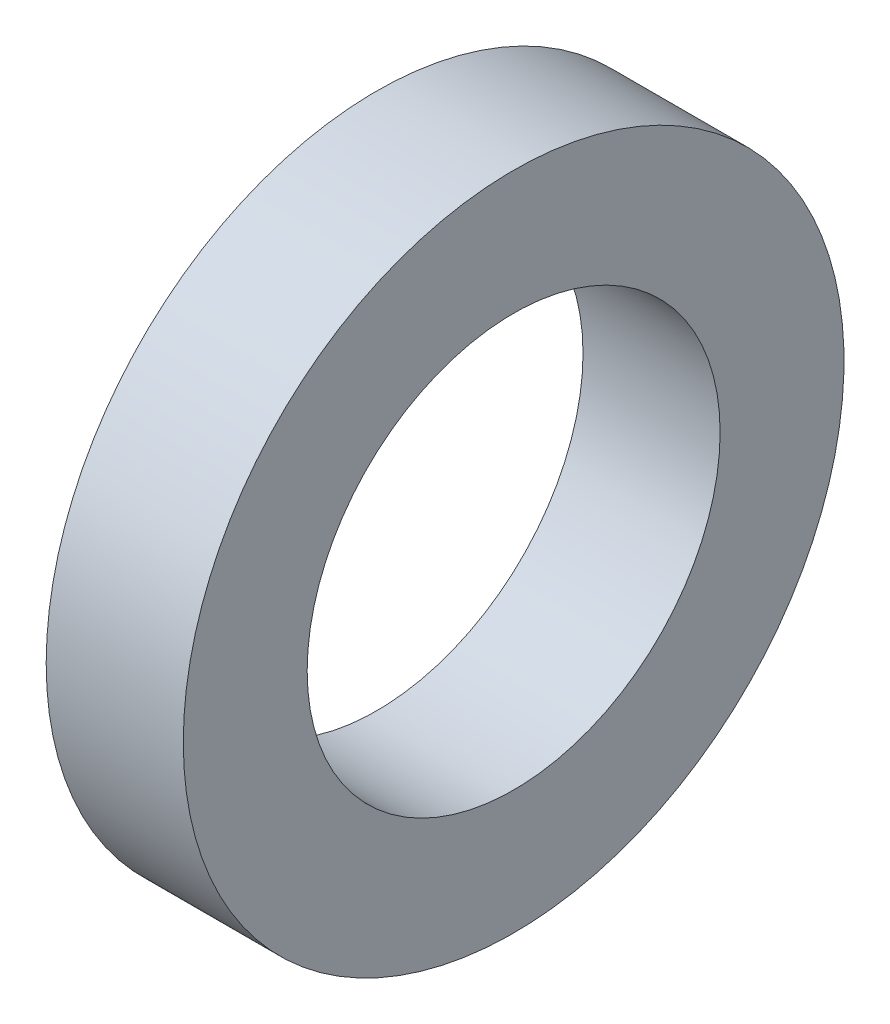
SolidWorks part; units mm, degrees
ref_plane "Front Plane" through (0, 0, 0) normal (0, 0, 1) x (1, 0, 0)
ref_plane "Top Plane" through (0, 0, 0) normal (0, 1, 0) x (1, 0, 0)
ref_plane "Right Plane" through (0, 0, 0) normal (1, 0, 0) x (0, 0, -1)
sketch "Sketch2" plane through (0, 0, 0) normal (0, 0, 1) x (1, 0, 0)
  line L0 (0, 0) -> (58.591, 0) construction
  line L2 (0, 0) -> (18.4, 0)
  line L3 (0, 0) -> (0, 2.5)
  line L4 (0, 2.5) -> (18.4, 2.5)
  line L5 (18.4, 0) -> (18.4, 2.5)
  line L6 (6, 2.5) -> (6, 6)
  line L11 (6, 6) -> (9.97, 6)
  line L16 (12.97, 6) -> (12.97, 3)
  line L17 (12.97, 3) -> (13.6304, 3)
  line L18 (13.6304, 3) -> (13.6304, 2.5)
  line L19 (13.6304, 2.5) -> (6, 2.5)
  line L22 (13.6304, 2.5) -> (16.1104, 2.5)
  line L23 (13.6304, 2.5) -> (13.6304, 4)
  line L24 (13.6304, 4) -> (16.1104, 4)
  line L25 (16.1104, 2.5) -> (16.1104, 4)
  line L27 (6, 6) -> (9.97, 6)
  line L28 (6, 6) -> (6, 9)
  line L29 (6, 9) -> (9.97, 9)
  line L30 (9.97, 6) -> (9.97, 9)
  line L31 (6, 9) -> (6, 8.25)
  line L32 (6, 8.25) -> (5, 8.25)
  line L33 (8.58, 22.001) -> (8.58, 12.476) construction
  line L34 (5, 12.476) -> (12.16, 12.476)
  line L35 (9.97, 9) -> (12.16, 9)
  line L36 (5, 7.5) -> (3, 7.5)
  line L37 (5, 8.25) -> (5, 12.476)
  line L38 (5, 7.5) -> (5, 14)
  line L39 (5, 14) -> (3, 14)
  line L40 (3, 7.5) -> (3, 14)
  line L41 (5, 22.001) -> (12.16, 22.001)
  line L42 (5, 22.001) -> (5, 30.1625)
  line L43 (5, 30.1625) -> (12.16, 30.1625)
  line L44 (12.16, 22.001) -> (12.16, 30.1625)
  line L49 (16.6304, 22.001) -> (16.6304, 7.5)
  line L51 (23.0104, 7.5) -> (23.0104, 6.5)
  line L54 (16.1104, 4) -> (13.6304, 4)
  line L56 (18.0304, 7.5) -> (23.0104, 7.5)
  line L57 (13.16, 22.001) -> (16.6304, 22.001)
  line L58 (16.1104, 3.5) -> (20.0104, 3.5)
  line L59 (29.9004, 14) -> (26.9004, 11)
  line L60 (4, 31.75) -> (18.0304, 31.75)
  line L61 (18.0304, 7.5) -> (23.0104, 7.5)
  line L62 (18.0304, 7.5) -> (18.0304, 12)
  line L63 (18.0304, 12) -> (23.0104, 12)
  line L64 (23.0104, 7.5) -> (23.0104, 12)
  line L65 (18.0304, 31.75) -> (18.0304, 12)
  line L66 (23.0104, 11) -> (26.9004, 11)
  line L67 (34.8004, 23) -> (31.3004, 19.5)
  line L68 (35.8004, 31) -> (38.7904, 33.99)
  line L69 (29.9004, 14) -> (29.9004, 15)
  line L70 (29.9004, 15) -> (22.9304, 15)
  line L71 (22.9304, 15) -> (21.0304, 15)
  line L72 (18.0304, 7.5) -> (16.6304, 7.5)
  line L73 (21.0304, 15) -> (21.0304, 43)
  line L74 (20.0304, 40) -> (10.0704, 40)
  line L75 (10.0704, 40) -> (4, 40)
  line L76 (21.0304, 43) -> (20.0304, 43)
  line L77 (22.9304, 15) -> (29.9004, 15)
  line L78 (22.9304, 15) -> (22.9304, 21)
  line L79 (22.9304, 21) -> (29.9004, 21)
  line L80 (29.9004, 15) -> (29.9004, 21)
  line L81 (10.0704, 40) -> (20.0304, 40)
  line L82 (10.0704, 40) -> (10.0704, 50)
  line L83 (10.0704, 50) -> (20.0304, 50)
  line L84 (20.0304, 40) -> (20.0304, 50)
  line L85 (4, 40) -> (4, 31.75)
  line L86 (12.97, 3) -> (12.97, 2.5)
  line L87 (31.3004, 19.5) -> (29.9004, 19.5)
  line L88 (21.51, 63.5) -> (21.51, 44)
  line L89 (21.51, 63.5) -> (25.9304, 63.5)
  line L90 (25.9304, 63.5) -> (25.9304, 25)
  line L91 (27.8304, 25) -> (25.9304, 25)
  line L92 (10.0704, 48) -> (9, 48)
  line L93 (9, 48) -> (9, 53.476)
  line L94 (9, 53.476) -> (20.0304, 53.476)
  line L95 (20.0304, 53.476) -> (20.0304, 50)
  line L96 (14.5152, 63.001) -> (14.5152, 53.476) construction
  line L97 (9, 63.001) -> (20.0304, 63.001)
  line L98 (9, 63.001) -> (9, 68.2625)
  line L99 (9, 68.2625) -> (20.0304, 68.2625)
  line L100 (20.0304, 63.001) -> (20.0304, 68.2625)
  line L101 (12.97, 6) -> (11.97, 6)
  line L102 (9, 42.5) -> (5, 42.5)
  line L103 (9, 42.5) -> (9, 55)
  line L104 (9, 55) -> (5, 55)
  line L105 (5, 42.5) -> (5, 55)
  line L106 (9.97, 6) -> (10.87, 6)
  line L107 (27.8304, 25) -> (34.8004, 25)
  line L108 (34.8004, 25) -> (34.8004, 23)
  line L109 (0, 0) -> (-2, 0)
  line L110 (0, 0) -> (0, 11)
  line L111 (27.8304, 25) -> (34.8004, 25)
  line L112 (27.8304, 25) -> (27.8304, 32.5)
  line L113 (27.8304, 32.5) -> (34.8004, 32.5)
  line L114 (34.8004, 25) -> (34.8004, 32.5)
  line L115 (35.8004, 31) -> (34.8004, 31)
  line L116 (27.8304, 32.5) -> (27.8304, 64.5)
  line L117 (21.1827, 74.025) -> (6.8477, 74.025)
  line L118 (6.8477, 74.025) -> (6.8477, 76.2)
  line L119 (38.7904, 47.29) -> (30.8304, 55.25)
  line L120 (0, 11) -> (-2, 11)
  line L121 (38.7904, 43.815) -> (30.8529, 43.815)
  line L123 (-4.8, 69.85) -> (1.55, 76.2)
  line L124 (38.7904, 47.29) -> (38.7904, 33.99)
  line L125 (-2, 0) -> (-2, 11)
  line L126 (38.7904, 37.465) -> (30.8529, 37.465)
  line L127 (30.8529, 43.815) -> (30.8529, 37.465)
  line L128 (6, 2.5) -> (6, 0)
  line L129 (0, 63.5) -> (0, 30)
  line L132 (5, 63.5) -> (0, 63.5)
  line L136 (-1.8, 30) -> (-11.76, 30)
  line L138 (-13.76, 25.4) -> (-2, 25.4)
  line L139 (-2, 25.4) -> (-2, 11.5)
  line L140 (27.8304, 64.5) -> (21.1827, 64.5)
  line L141 (-1.8, 30) -> (-11.76, 30)
  line L142 (-1.8, 30) -> (-1.8, 39)
  line L143 (-1.8, 39) -> (-11.76, 39)
  line L144 (-11.76, 30) -> (-11.76, 39)
  line L145 (21.1827, 64.5) -> (21.1827, 74.025)
  line L146 (-12.76, 37) -> (-12.76, 47.29)
  line L147 (-12.76, 37) -> (-11.76, 37)
  line L148 (30.8304, 55.25) -> (30.8304, 76.2)
  line L149 (11.97, 6) -> (11.97, 5.45)
  line L154 (-2, 11.5) -> (1, 11.5)
  line L155 (5, 60.6197) -> (24.05, 60.6197)
  line L160 (5, 60.6197) -> (5, 55.8572)
  line L161 (5, 55.8572) -> (24.05, 55.8572)
  line L166 (24.05, 60.6197) -> (24.05, 55.8572)
  line L167 (5, 60.6197) -> (24.05, 55.8572) construction
  line L172 (5, 55.8572) -> (24.05, 60.6197) construction
  line L173 (24.05, 62.2072) -> (25.9304, 62.2072)
  line L174 (11.97, 5.45) -> (10.87, 5.45)
  line L175 (10.87, 6) -> (10.87, 5.45)
  line L176 (24.05, 62.2072) -> (24.05, 54.2697)
  line L177 (24.05, 54.2697) -> (25.9304, 54.2697)
  line L178 (25.9304, 62.2072) -> (25.9304, 54.2697)
  line L179 (24.05, 62.2072) -> (25.9304, 54.2697) construction
  line L180 (24.05, 54.2697) -> (25.9304, 62.2072) construction
  line L181 (3, 19.6197) -> (15.7, 19.6197)
  line L182 (3, 19.6197) -> (3, 14.8572)
  line L183 (3, 14.8572) -> (15.7, 14.8572)
  line L184 (15.7, 19.6197) -> (15.7, 14.8572)
  line L185 (3, 19.6197) -> (15.7, 14.8572) construction
  line L186 (3, 14.8572) -> (15.7, 19.6197) construction
  line L187 (15.7, 21.2072) -> (16.6304, 21.2072)
  line L188 (15.7, 21.2072) -> (15.7, 13.2697)
  line L189 (15.7, 13.2697) -> (16.6304, 13.2697)
  line L190 (16.6304, 21.2072) -> (16.6304, 13.2697)
  line L191 (15.7, 21.2072) -> (16.6304, 13.2697) construction
  line L192 (15.7, 13.2697) -> (16.6304, 21.2072) construction
  line L193 (1, 11.5) -> (1, 6.5)
  line L194 (1, 6.5) -> (3, 6.5)
  line L195 (23.0104, 6.5) -> (20.0104, 3.5)
  line L196 (5, 63.5) -> (5, 42.5)
  line L197 (5, 42.5) -> (3, 42.5)
  line L198 (3, 42.5) -> (3, 6.5)
  line L199 (6, 0) -> (12.97, 0)
  line L200 (12.97, 0) -> (12.97, 2.5)
  line L201 (18.0304, 31.75) -> (18.0304, 35.875)
  line L202 (18.0304, 35.875) -> (21.0304, 35.875)
  line L203 (30.8304, 76.2) -> (6.8477, 76.2)
  line L204 (3.4027, 69.85) -> (7.8477, 69.85) construction
  line L205 (7.8477, 67.4687) -> (26.8977, 67.4688)
  line L206 (7.8477, 74.025) -> (7.8477, 64.5)
  line L207 (7.8477, 64.5) -> (-1.8, 64.5)
  line L208 (-1.8, 64.5) -> (-1.8, 39)
  line L209 (-12.76, 47.29) -> (-4.8, 55.25)
  line L210 (-4.8, 55.25) -> (-4.8, 69.85)
  line L211 (7.8477, 67.4687) -> (7.8477, 72.2313)
  line L212 (7.8477, 72.2313) -> (26.8977, 72.2313)
  line L213 (26.8977, 67.4688) -> (26.8977, 72.2313)
  line L214 (26.8977, 73.8187) -> (30.8304, 73.8187)
  line L215 (26.8977, 73.8187) -> (26.8977, 65.8813)
  line L216 (26.8977, 65.8813) -> (30.8304, 65.8813)
  line L217 (30.8304, 73.8187) -> (30.8304, 65.8813)
  line L218 (3.4027, 72.2313) -> (25.6277, 72.2313)
  line L219 (3.4027, 72.2313) -> (3.4027, 67.4687)
  line L220 (3.4027, 67.4687) -> (25.6277, 67.4687)
  line L221 (25.6277, 72.2313) -> (25.6277, 67.4687)
  line L222 (25.6277, 69.85) -> (21.1827, 69.85) construction
  line L223 (21.51, 44) -> (22.9304, 44)
  line L224 (22.9304, 44) -> (22.9304, 21)
  line L225 (13.6304, 4) -> (13.6304, 12.2697)
  line L226 (13.6304, 12.2697) -> (13.16, 12.2697)
  line L227 (13.16, 12.2697) -> (13.16, 22.001)
  line L228 (12.16, 9) -> (12.16, 12.476)
  line L229 (-1.8, 30) -> (0, 30)
  line L230 (9, 65.6317) -> (3.4027, 65.6317) construction
  line L231 (20.0304, 65.6317) -> (25.6277, 65.6317) construction
  line L232 (1.55, 76.2) -> (6.8477, 76.2)
  line L233 (-11.76, 30) -> (-13.76, 30)
  line L234 (-13.76, 30) -> (-13.76, 25.4)
  circle A0 centre (26.8804, 25.95) radius 0.95
  circle A1 centre (21.9804, 15.95) radius 0.95
  circle A2 centre (17.3304, 8.2) radius 0.7
  circle A3 centre (10.42, 6.45) radius 0.45
  circle A4 centre (-0.9, 30.9) radius 0.9
  point P7 (24.9902, 58.2385)
  point P131 (16.1652, 17.2385)
  point P135 (14.525, 58.2385)
  point P146 (9.35, 17.2385)
sketch "Sketch3" plane through (0, 0, 0) normal (0, 0, 1) x (1, 0, 0)
  line L0 (18.0304, 12) -> (23.0104, 12) construction
  line L1 (18.0304, 7.5) -> (23.0104, 7.5) construction
  line L2 (18.0304, 7.5) -> (18.0304, 12) construction
  line L3 (23.0104, 7.5) -> (23.0104, 12) construction
  line L4 (18.0304, 12) -> (23.0104, 12)
  line L5 (18.0304, 7.5) -> (23.0104, 7.5)
  line L6 (18.0304, 7.5) -> (18.0304, 12)
  line L7 (23.0104, 7.5) -> (23.0104, 12)
revolve "Revolve1" add sketch "Sketch3" angle 360 about L0
